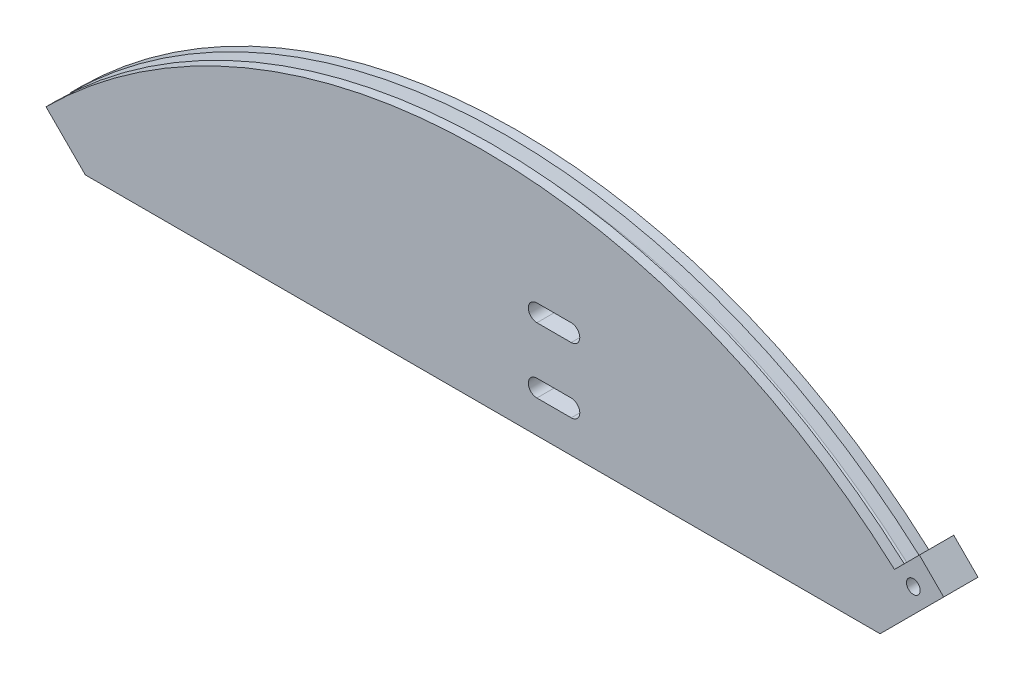
SolidWorks part; units mm, degrees
ref_plane "Plan de face" through (0, 0, 0) normal (0, 0, 1) x (1, 0, 0)
ref_plane "Plan de dessus" through (0, 0, 0) normal (0, 1, 0) x (1, 0, 0)
ref_plane "Plan de droite" through (0, 0, 0) normal (1, 0, 0) x (0, 0, -1)
sketch "Esquisse1" plane through (0, 0, 0) normal (0, 0, 1) x (1, 0, 0)
  line L0 (0, 0) -> (0, 183.9945) construction
  line L1 (-120.2082, 115.8148) -> (120.2082, 115.8148)
  line L2 (-8.623, 115.8148) -> (4.3475, 115.8148) construction
  line L3 (120.2082, 115.8148) -> (120.2082, 120.2082)
  line L4 (-120.2082, 115.8148) -> (-120.2082, 120.2082)
  arc A1 (-120.2082, 120.2082) -> (120.2082, 120.2082) centre (0, 0) cw
  point P10 (0, 115.8148)
  dimension "D1" = 90
  dimension "D2" = 170
extrude "Boss.-Extru.1" add sketch "Esquisse1" along normal blind 5
sketch "Esquisse2" plane through (0, 0, 0) normal (0, 0, -1) x (-1, 0, 0)
  line L0 (127.2792, 127.2792) -> (120.2082, 120.2082)
  line L1 (-127.2792, 127.2792) -> (-120.2082, 120.2082)
  line L5 (-120.2082, 120.2082) -> (-120.2082, 115.8148)
  line L6 (-120.2082, 115.8148) -> (120.2082, 115.8148)
  line L7 (120.2082, 115.8148) -> (120.2082, 120.2082)
  arc A2 (127.2792, 127.2792) -> (-127.2792, 127.2792) centre (0, 0) ccw
  arc A3 (127.2792, 127.2792) -> (-127.2792, 127.2792) centre (0, 0) ccw
  arc A4 (120.2082, 120.2082) -> (-120.2082, 120.2082) centre (0, 0) ccw
  arc A5 (120.2082, 120.2082) -> (-120.2082, 120.2082) centre (0, 0) ccw
  dimension "D1" = 10
  dimension "D2" = 0
extrude "Boss.-Extru.2" add sketch "Esquisse2" along normal blind 5 and the other way blind 5
sketch "Esquisse3" plane through (0, 0, 0) normal (0, 0, -1) x (-1, 0, 0)
  arc A2 (126.5721, 126.5721) -> (-126.5721, 126.5721) centre (0, 0) ccw
  arc A3 (126.5721, 126.5721) -> (-126.5721, 126.5721) centre (0, 0) ccw
  dimension "D1" = 1
sketch "Esquisse5" plane through (0, 0, 0) normal (0.7071, -0.7071, 0) x (0, 0, -1)
  line L1 (-0.9397, 176.658) -> (-2.1561, 180)
  line L3 (0, 0) -> (0, 179) construction
  line L4 (-5, 180) -> (5, 180) construction
  line L5 (0.9397, 176.658) -> (2.1561, 180)
  line L6 (2.1561, 180) -> (-2.1561, 180)
  arc A0 (-0.9397, 176.658) -> (0.9397, 176.658) centre (0, 177) ccw
  dimension "D1" = 70
  dimension "D2" = 1
  dimension "D3" = 3
sweep "Enlèvement de matière-Balayage1" cut profiles "Esquisse5" path "Esquisse3"
sketch "Esquisse7" plane through (0, 0, 0) normal (0, 0, -1) x (-1, 0, 0)
  line L0 (-123.7437, 123.7437) -> (-134.3503, 134.3503)
  line L1 (-127.2792, 127.2792) -> (-120.2082, 120.2082) construction
  line L2 (-134.3503, 134.3503) -> (-127.2792, 141.4214)
  line L3 (-127.2792, 141.4214) -> (-116.6726, 130.8148)
  line L4 (-116.6726, 130.8148) -> (-123.7437, 123.7437)
  line L5 (-127.2792, 141.4214) -> (-123.7437, 123.7437) construction
  circle A2 centre (-125.5115, 132.5825) radius 2
  dimension "D4" = 4
  dimension "D1" = 10
  dimension "D2" = 15
  dimension "D3" = 5
extrude "Boss.-Extru.3" add sketch "Esquisse7" along normal blind 5 and the other way blind 5
sketch "Esquisse8" plane through (0, 0, 0) normal (0, 0, -1) x (-1, 0, 0)
  line L0 (-120.2082, 120.2082) -> (-104.6304, 104.6304)
  line L1 (-104.6304, 104.6304) -> (-145.0231, 109.5353)
  line L2 (-145.0231, 109.5353) -> (-125.1246, 125.1246)
  line L3 (-134.3503, 134.3503) -> (-120.2082, 120.2082) construction
  line L4 (-125.1246, 125.1246) -> (-120.2082, 120.2082)
  line L5 (127.2792, 127.2792) -> (100.7415, 100.7415)
  line L6 (100.7415, 100.7415) -> (140.5078, 93.2466)
  line L7 (140.5078, 93.2466) -> (127.2792, 127.2792)
extrude "Enlèv. mat.-Extru.4" cut sketch "Esquisse8" against normal through all and the other way through all
sketch "Esquisse9" plane through (0, 0, 0) normal (0, 0, -1) x (-1, 0, 0)
  line L0 (-20.7912, 146.8148) -> (-20.7912, 127.8148) construction
  line L1 (-17.7912, 146.8148) -> (-17.7912, 127.8148)
  line L2 (-23.7912, 146.8148) -> (-23.7912, 127.8148)
  arc A0 (-17.7912, 146.8148) -> (-23.7912, 146.8148) centre (-20.7912, 146.8148) ccw
  arc A1 (-17.7912, 127.8148) -> (-23.7912, 127.8148) centre (-20.7912, 127.8148) cw
  dimension "D1" = 3
extrude "Enlèv. mat.-Extru.5" [suppressed] cut sketch "Esquisse9" against normal through all and the other way through all
sketch "Esquisse10" plane through (0, 0, 0) normal (0, 0, -1) x (-1, 0, 0)
  line L0 (-25.7912, 146.8148) -> (-15.7912, 146.8148) construction
  line L1 (-20.7912, 137.3148) -> (-3.9914, 137.3148) construction
  line L2 (-25.7912, 149.3148) -> (-15.7912, 149.3148)
  line L3 (115.8148, 115.8148) -> (-115.8148, 115.8148) construction
  line L4 (-20.7912, 146.8148) -> (-20.7912, 127.8148) construction
  line L6 (-25.7912, 144.3148) -> (-15.7912, 144.3148)
  line L13 (-25.7912, 127.8148) -> (-15.7912, 127.8148) construction
  line L14 (-25.7912, 130.3148) -> (-15.7912, 130.3148)
  line L15 (-25.7912, 125.3148) -> (-15.7912, 125.3148)
  arc A0 (-15.7912, 144.3148) -> (-15.7912, 149.3148) centre (-15.7912, 146.8148) ccw
  arc A1 (-25.7912, 130.3148) -> (-25.7912, 125.3148) centre (-25.7912, 127.8148) ccw
  arc A2 (-25.7912, 144.3148) -> (-25.7912, 149.3148) centre (-25.7912, 146.8148) cw
  arc A3 (-15.7912, 130.3148) -> (-15.7912, 125.3148) centre (-15.7912, 127.8148) cw
  point P3 (-20.7912, 144.3148)
  point P12 (-20.7912, 149.3148)
  point P21 (-20.7912, 125.3148)
  point P22 (-20.7912, 130.3148)
  dimension "D1" = 5
  dimension "D2" = 5
  dimension "D3" = 9.5
  dimension "D4" = 16.7998
extrude "Enlèv. mat.-Extru.6" cut sketch "Esquisse10" against normal through all and the other way through all
chamfer "Chanfrein1" distance 0.5 angle 45 1 edges at (0, 115.8148, 0)
